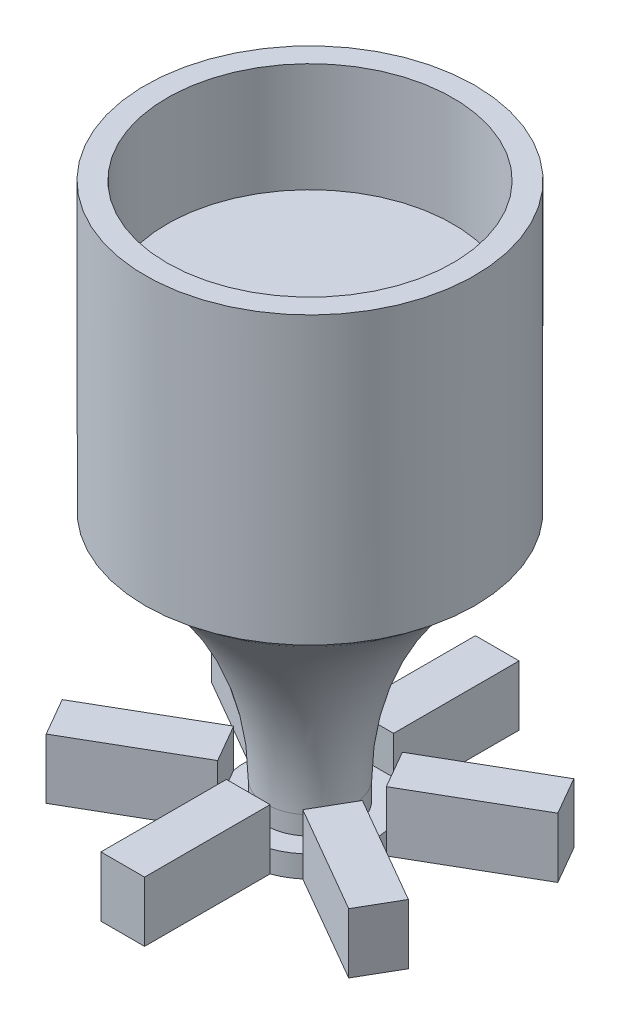
SolidWorks part; units mm, degrees
ref_plane "Front Plane" through (0, 0, 0) normal (0, 0, 1) x (1, 0, 0)
ref_plane "Top Plane" through (0, 0, 0) normal (0, 1, 0) x (1, 0, 0)
ref_plane "Right Plane" through (0, 0, 0) normal (1, 0, 0) x (0, 0, -1)
sketch "Sketch1" plane through (0, 0, 0) normal (0, 1, 0) x (1, 0, 0)
  line L48 (-2, -5.6569) -> (2, -5.6569)
  line L55 (2, -5.6569) -> (2, -17.1569)
  line L62 (2, -17.1569) -> (-2, -17.1569)
  line L69 (-2, -17.1569) -> (-2, -5.6569)
  line L70 (-15.8583, -6.8464) -> (-5.899, -1.0964)
  line L71 (-5.899, -1.0964) -> (-3.899, -4.5605)
  line L72 (-3.899, -4.5605) -> (-13.8583, -10.3105)
  line L73 (-13.8583, -10.3105) -> (-15.8583, -6.8464)
  line L74 (-13.8583, 10.3105) -> (-3.899, 4.5605)
  line L75 (-3.899, 4.5605) -> (-5.899, 1.0964)
  line L76 (-5.899, 1.0964) -> (-15.8583, 6.8464)
  line L77 (-15.8583, 6.8464) -> (-13.8583, 10.3105)
  line L78 (2, 17.1569) -> (2, 5.6569)
  line L79 (2, 5.6569) -> (-2, 5.6569)
  line L80 (-2, 5.6569) -> (-2, 17.1569)
  line L81 (-2, 17.1569) -> (2, 17.1569)
  line L82 (15.8583, 6.8464) -> (5.899, 1.0964)
  line L83 (5.899, 1.0964) -> (3.899, 4.5605)
  line L84 (3.899, 4.5605) -> (13.8583, 10.3105)
  line L85 (13.8583, 10.3105) -> (15.8583, 6.8464)
  line L86 (13.8583, -10.3105) -> (3.899, -4.5605)
  line L87 (3.899, -4.5605) -> (5.899, -1.0964)
  line L88 (5.899, -1.0964) -> (15.8583, -6.8464)
  line L89 (15.8583, -6.8464) -> (13.8583, -10.3105)
  circle A2 centre (0, 0) radius 4
  arc A3 (2, -5.6569) -> (3.899, -4.5605) centre (0, 0) ccw
  arc A4 (-3.899, -4.5605) -> (-2, -5.6569) centre (0, 0) ccw
  arc A5 (-5.899, 1.0964) -> (-5.899, -1.0964) centre (0, 0) ccw
  arc A6 (-2, 5.6569) -> (-3.899, 4.5605) centre (0, 0) ccw
  arc A7 (3.899, 4.5605) -> (2, 5.6569) centre (0, 0) ccw
  arc A8 (5.899, -1.0964) -> (5.899, 1.0964) centre (0, 0) ccw
  point P9 (0, -5.6569)
  point P31 (0, 0)
  point P32 (0, 0)
  point P33 (0, 0)
  point P46 (0.0289, 0.0554)
  dimension "D1" = 8
  dimension "D3" = 2
  dimension "D4" = 4
  dimension "D5" = 11.5
  dimension "D6" = 6
extrude "Boss-Extrude1" add sketch "Sketch1" along normal blind 25 contours A2
extrude "Boss-Extrude2" add sketch "Sketch1<3>" along normal blind 5.5 contours L62 | L69 L48 L55 L62 | L70 L71 L72 L73 | L74 L75 L76 L77 | L78 L79 L80 L81 | L82 L83 L84 L85 | L86 L87 L88 L89
sketch "Sketch1<3>" plane through (0, 0, 0) normal (0, 1, 0) x (1, 0, 0) same geometry as "Sketch1"
extrude "Boss-Extrude3" add sketch "Sketch1<4>" along normal blind 2 contours L87 A8 L83 A7 L79 A6 L75 A5 L71 A4 L48 A3 A2 region at (-2.9175, 0, 5.0533)
sketch "Sketch1<4>" plane through (0, 0, 0) normal (0, 1, 0) x (1, 0, 0) same geometry as "Sketch1"
combine bodies "Combine1" operation type add bodies to combine 125 126 127 128 123 124 121
sketch "Sketch2" plane through (0, 25, 0) normal (0, 1, 0) x (1, 0, 0)
  circle A1 centre (0, 0) radius 15.1
  circle A3 centre (0, 0) radius 13.1
  dimension "D1" = 2
  dimension "D2" = 26.2
extrude "Boss-Extrude6" add sketch "Sketch2" along normal blind 26.2 separate body contours A1
sketch "Sketch3" plane through (0, 51.2, 0) normal (0, 1, 0) x (1, 0, 0)
  circle A0 centre (0, 0) radius 13.1
  circle A2 centre (0, 0) radius 15.1 construction
  dimension "D1" = 2
extrude "Cut-Extrude1" cut sketch "Sketch3" against normal blind 10
combine bodies "Combine3" operation type add bodies to combine 137 129
fillet "Fillet1" radius 26 1 edges at (0, 25, 4)
